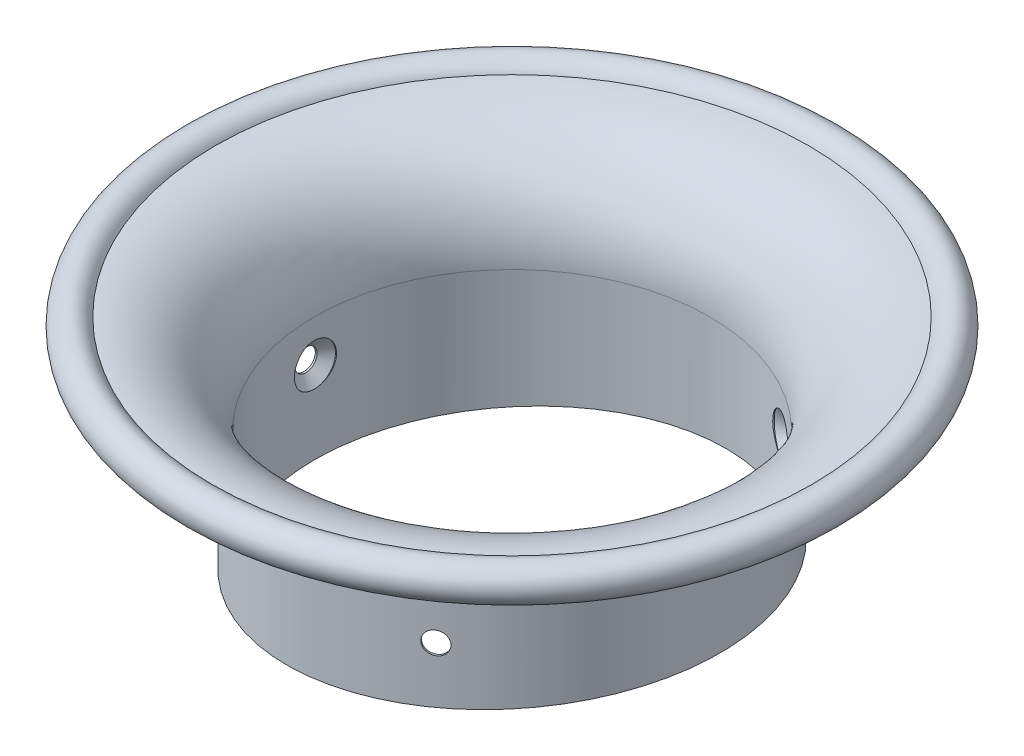
SolidWorks part; units mm, degrees
ref_plane "Front Plane" through (0, 0, 0) normal (0, 0, 1) x (1, 0, 0)
ref_plane "Top Plane" through (0, 0, 0) normal (0, 1, 0) x (1, 0, 0)
ref_plane "Right Plane" through (0, 0, 0) normal (1, 0, 0) x (0, 0, -1)
sketch "Sketch1" plane through (0, 0, 0) normal (0, 0, 1) x (1, 0, 0)
  line L13 (0, -32.9325) -> (0, 32.9325) construction
  line L14 (0, -32.9325) -> (-60.325, -32.9325) construction
  line L16 (-60.325, -32.9325) -> (-60.325, 5.3493)
  line L17 (-60.325, -32.9325) -> (-63.5, -32.9325)
  line L18 (-63.5, -32.9325) -> (-63.5, 2.1743)
  line L22 (-63.5, 2.1743) -> (-66.675, 2.1743)
  line L23 (-66.675, 5.3493) -> (-66.675, 2.1743)
  line L26 (-80.5158, 32.9325) -> (-86.8658, 32.9325)
  line L28 (0, 32.9325) -> (-86.8658, 32.9325) construction
  arc A2 (-60.325, 5.3493) -> (-79.4176, 32.7365) centre (-89.514, 5.3493) ccw
  arc A3 (-66.675, 5.3493) -> (-86.8658, 28.0342) centre (-89.514, 5.3493) ccw
  arc A4 (-86.8658, 32.9325) -> (-86.8658, 28.0342) centre (-86.4912, 30.4833) ccw
  arc A8 (-60.325, 5.3493) -> (-86.1295, 34.3414) centre (-89.514, 5.3493) ccw construction
  arc A9 (-79.4176, 32.7365) -> (-80.5158, 32.9325) centre (-80.5158, 29.7575) ccw
  point P1 (0, 0)
  point P3 (0, 0)
  point P16 (-87.0002, 37.8619)
  point P17 (-60.325, -25.5818)
  point P22 (-86.8658, 40.2783)
  point P23 (0, 0)
  point P24 (-86.8658, 40.2826)
  point P25 (-65.7144, 40.0872)
  point P26 (-87.6726, 40.0119)
  point P27 (0, 0)
  point P28 (-60.325, -18.2542)
  point P29 (0, 0)
  point P30 (0, 33.2646)
  point P31 (0, 0)
  point P32 (0, -32.9325)
  point P33 (0, -32.9325)
  dimension "D8" = 3.175
  dimension "D9" = 22.839
  dimension "D10" = 2.4776
  dimension "D3" = 3.175
  dimension "D4" = 35.1068
  dimension "D6" = 6.35
  dimension "D7" = 6.35
  dimension "D11" = 25.8599
sketch "Sketch2" plane through (0, 0, 0) normal (0, 0, 1) x (1, 0, 0)
  line L0 (0, 0) -> (0, 25.4) construction
  line L1 (0, 0) -> (-25.4, 0) construction
  line L2 (-25.4, 0) -> (-25.4, 25.4) construction
  line L3 (-25.4, 30.1625) -> (-25.4, 25.4) construction
  line L4 (-25.4, 27.7812) -> (-30.1625, 27.7812) construction
  line L5 (0, 0) -> (1.5875, 0)
  line L6 (1.5875, 0) -> (1.5875, -38.1)
  line L7 (1.5875, -38.1) -> (4.7625, -38.1)
  line L8 (4.7625, -38.1) -> (4.7625, 0)
  line L9 (1.5875, -38.1) -> (65.0875, -38.1) construction
  line L10 (65.0875, -38.1) -> (65.0875, 33.1059) construction
  line L11 (-30.1625, 33.1059) -> (65.0875, 33.1059) construction
  arc A0 (0, 0) -> (-25.4, 25.4) centre (-25.4, 0) ccw
  arc A1 (4.7625, 0) -> (-25.4, 30.1625) centre (-25.4, 0) ccw
  arc A2 (-25.4, 30.1625) -> (-25.4, 25.4) centre (-30.1625, 27.7812) ccw
  arc A3 (-25.4, 25.4) -> (-25.4, 30.1625) centre (-30.1625, 27.7812) ccw construction
  point P18 (0, 0)
  dimension "D1" = 25.4
  dimension "D3" = 4.7625
  dimension "D4" = 38.1
  dimension "D5" = 3.175
  dimension "D6" = 127
  dimension "D2" = 4.7625
revolve "RevolvedVenturi-5inchOutsideDiaLower_2inchDeep" add sketch "Sketch2" angle 360 about L10
sketch "Sketch3" plane through (0, 0, 0) normal (0, 0, 1) x (1, 0, 0)
  line L0 (1.5875, -38.1) -> (128.5875, -38.1) construction
  line L1 (128.5875, -38.1) -> (305.2706, -38.1) construction
  line L2 (305.2706, -38.1) -> (305.2706, -11.5312) construction
  line L3 (305.2706, -11.5312) -> (1.5875, -38.1)
  line L4 (1.5875, -38.1) -> (5.8933, -87.316)
  line L5 (5.8933, -87.316) -> (309.5764, -60.7472)
  line L6 (309.5764, -60.7472) -> (305.2706, -11.5312)
  point P0 (161.0463, 66.1625)
  point P5 (1.5875, -38.1)
  dimension "D1" = 85
extrude "Cut-Extrude1" cut sketch "Sketch3" against normal through all both and the other way through all
hole_wizard "CSK for 1/4 Flat Head Machine Screw (100)1" positions "3DSketch1" profile "Sketch5" countersink size "1/4" standard "ANSI Inch" end condition up to next
sketch3d "3DSketch1"
  line L0 (65.0875, 0, 0) -> (4.7625, 0, 0) construction
  line L2 (4.7625, 0, 0) -> (4.7625, -12.7, 0) construction
  circle A0 centre (65.0875, 0, 0) radius 60.325 construction
  point P5 (65.0875, -60.325, 0)
  point P12 (4.7625, -12.7, 0)
  point P16 (4.7625, -12.7, 0)
  point P18 (4.7625, -12.7, 0)
  point P22 (4.7625, -12.7, 0)
  point P25 (0, 0, 0)
  dimension "D1" = 12.7
sketch "Sketch5" plane through (4.7625, -12.7, 0) normal (0, 1, 0) x (0, 0, -1)
  line L0 (0, 0) -> (0, 26.419)
  line L1 (0, 26.419) -> (3.3782, 26.419)
  line L2 (3.3782, 26.419) -> (3.3782, 2.5682)
  line L3 (3.3782, 2.5682) -> (6.4389, 0)
  line L5 (6.4389, 0) -> (0, 0)
  line L6 (-3.3782, 2.5682) -> (-6.4389, 0) construction
  line L11 (0, -6.35) -> (0, 107.95) construction
  dimension "Thru Hole Dia." = 6.7564
  dimension "Thru Hole Depth" = 26.419
  dimension "Near C'Sink Dia." = 12.8778
  dimension "Near C'Sink Angle" = 100
pattern_circular "CirPattern1" count 3 over 360 about axis through (65.0875, 0, 0) along (0, -1, 0) of "CSK for 1/4 Flat Head Machine Screw (100)1"
